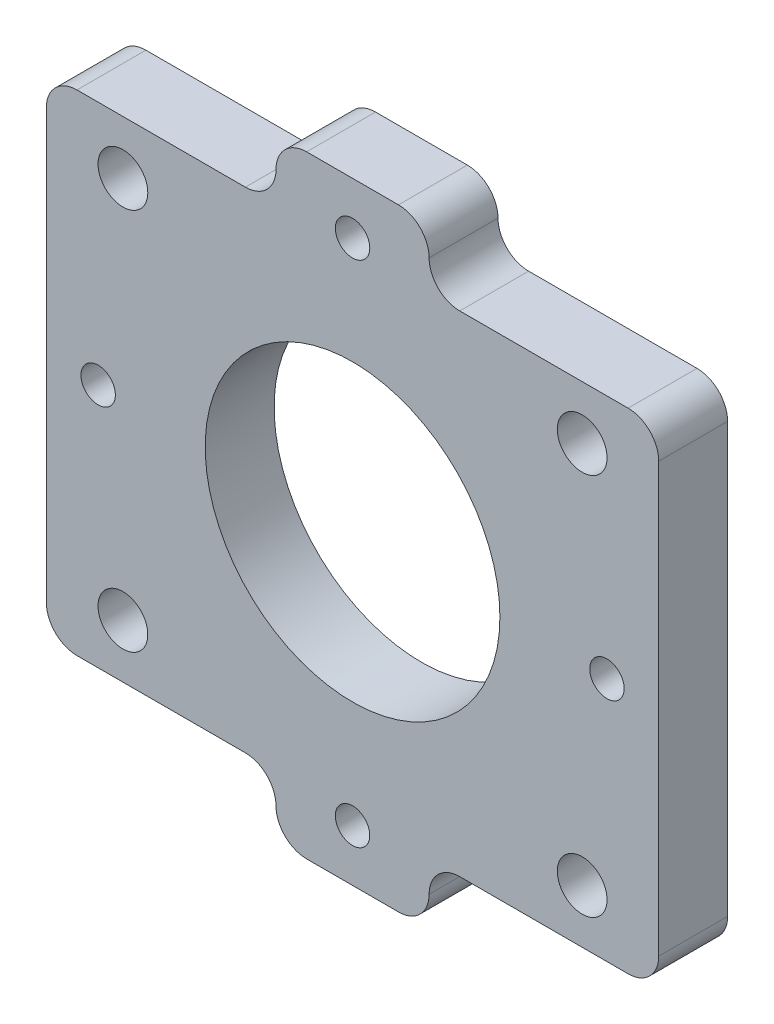
SolidWorks part; units mm, degrees
ref_plane "Front" through (0, 0, 0) normal (0, 0, 1) x (1, 0, 0)
ref_plane "Top" through (0, 0, 0) normal (0, 1, 0) x (1, 0, 0)
ref_plane "Right" through (0, 0, 0) normal (1, 0, 0) x (0, 0, -1)
sketch "Esquisse1" plane through (0, 0, 0) normal (0, 0, 1) x (1, 0, 0)
  line L1 (0, 0) -> (80, 0)
  line L2 (0, 0) -> (0, 80)
  line L3 (0, 80) -> (80, 80)
  line L4 (80, 0) -> (80, 80)
  dimension "D1" = 80
  dimension "D2" = 80
extrude "Boss.-Extru.1" add sketch "Esquisse1" along normal blind 9
sketch "Esquisse2" plane through (0, 0, 9) normal (0, 0, 1) x (1, 0, 0)
  line L0 (40, 80) -> (40, 0) construction
  line L1 (80, 80) -> (0, 80) construction
  line L2 (0, 0) -> (80, 0) construction
  line L3 (0, 80) -> (0, 0) construction
  line L4 (40, 40) -> (73.234, 40) construction
  line L5 (73.234, 40) -> (40, 73.234) construction
  line L6 (40, 40) -> (42.7843, 37.2157) construction
  line L7 (40, 6.766) -> (6.766, 40) construction
  line L8 (40, 40) -> (40, 6.766) construction
  circle A0 centre (40, 40) radius 19.25
  circle A1 centre (73.234, 40) radius 2.25
  circle A2 centre (40, 73.234) radius 2.25
  circle A3 centre (6.766, 40) radius 2.25
  circle A4 centre (40, 6.766) radius 2.25
  circle A5 centre (10, 65) radius 3.25
  circle A6 centre (70, 65) radius 3.25
  circle A7 centre (70, 15) radius 3.25
  circle A8 centre (10, 15) radius 3.25
  dimension "D2" = 38.5
  dimension "D4" = 4.5
  dimension "D9" = 6.5
  dimension "D1" = 40
  dimension "D3" = 90
  dimension "D5" = 45
  dimension "D6" = 47
  dimension "D7" = 60
  dimension "D8" = 50
extrude "Enlèv. mat.-Extru.1" cut sketch "Esquisse2" against normal through all
sketch "Esquisse3" plane through (0, 0, 9) normal (0, 0, 1) x (1, 0, 0)
  line L0 (40, 80) -> (40, 0) construction
  line L1 (80, 80) -> (0, 80) construction
  line L2 (0, 0) -> (80, 0) construction
  line L3 (40, 40) -> (80, 40) construction
  line L4 (80, 0) -> (80, 80) construction
  line L5 (0, 80) -> (0, 72)
  line L6 (50, 80) -> (80, 80)
  line L7 (50, 80) -> (50, 72)
  line L8 (50, 72) -> (80, 72)
  line L9 (80, 80) -> (80, 72)
  line L10 (30, 72) -> (0, 72)
  line L11 (30, 80) -> (30, 72)
  line L12 (30, 80) -> (0, 80)
  line L13 (30, 0) -> (0, 0)
  line L14 (30, 0) -> (30, 8)
  line L15 (30, 8) -> (0, 8)
  line L16 (80, 0) -> (80, 8)
  line L17 (50, 8) -> (80, 8)
  line L18 (50, 0) -> (50, 8)
  line L19 (50, 0) -> (80, 0)
  line L20 (0, 0) -> (0, 8)
  dimension "D1" = 8
  dimension "D2" = 10
extrude "Enlèv. mat.-Extru.2" cut sketch "Esquisse3" against normal through all both and the other way through all
fillet "Congé1" radius 4 12 edges at (30, 72, 4.5) (50, 72, 4.5) (50, 8, 4.5) (30, 8, 4.5) (0, 8, 4.5) (30, 0, 4.5) (50, 0, 4.5) (80, 8, 4.5) (80, 72, 4.5) (50, 80, 4.5) (30, 80, 4.5) (0, 72, 4.5)
